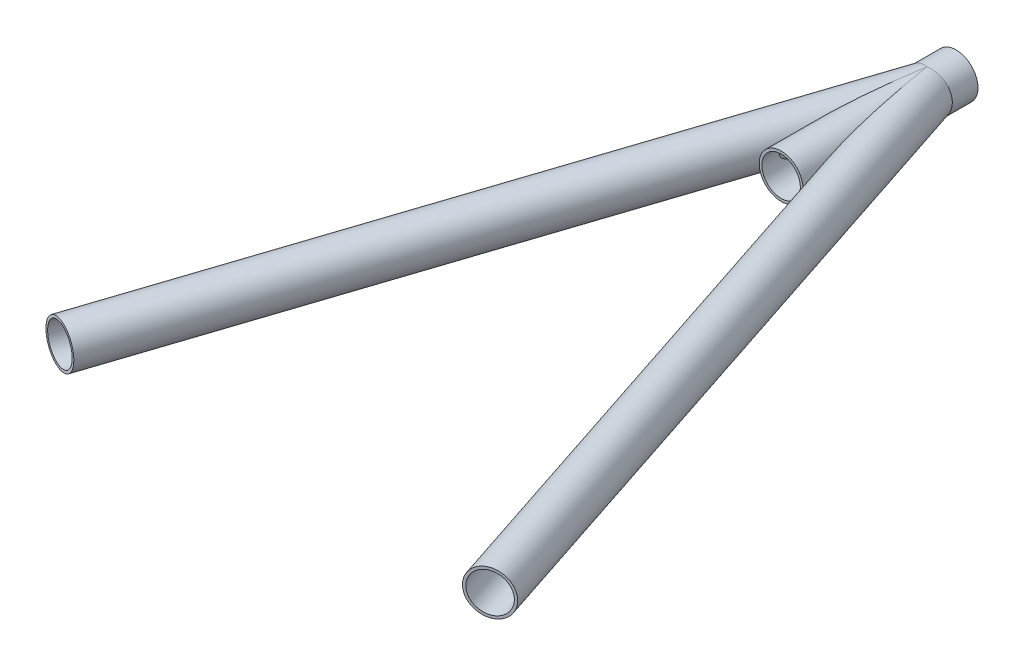
SolidWorks part; units mm, degrees
ref_plane "Front Plane" through (0, 0, 0) normal (0, 0, 1) x (1, 0, 0)
ref_plane "Top Plane" through (0, 0, 0) normal (0, 1, 0) x (1, 0, 0)
ref_plane "Right Plane" through (0, 0, 0) normal (1, 0, 0) x (0, 0, -1)
sketch "Sketch1" plane through (0, 0, 0) normal (0, 1, 0) x (1, 0, 0)
  line L0 (0, 0) -> (0, -25.4) construction
  line L1 (0, -25.4) -> (0, -38.1) construction
  line L2 (0, 0) -> (0, -346.075) construction
  line L3 (0, -38.1) -> (101.6, -346.075) construction
  line L4 (0, -38.1) -> (-101.6, -346.075) construction
  line L5 (101.6, -346.075) -> (0, -346.075) construction
  line L6 (0, -346.075) -> (-101.6, -346.075) construction
  line L7 (-101.6, -346.075) -> (-93.6425, -321.9537) construction
  line L8 (101.6, -346.075) -> (93.6425, -321.9537) construction
  line L9 (0, -38.1) -> (0, -101.6) construction
  circle A0 centre (0, 0) radius 15.003 construction
  circle A1 centre (101.6, -346.075) radius 15.003 construction
  circle A2 centre (-101.6, -346.075) radius 15.003 construction
  dimension "D1" = 25.4
  dimension "D2" = 101.6
  dimension "D3" = 346.075
  dimension "D4" = 25.4
  dimension "D5" = 25.4
  dimension "D6" = 12.7
  dimension "D7" = 63.5
ref_plane "Plane1" through (0, 0, 25.4) normal (0, 0, 1) x (1, 0, 0)
sketch "Sketch2" plane through (0, 0, 25.4) normal (0, 0, 1) x (1, 0, 0)
  circle A0 centre (0, 0) radius 9.525
  circle A1 centre (0, 0) radius 8.382
  dimension "D1" = 19.05
  dimension "D2" = 1.143
extrude "Boss-Extrude1" add sketch "Sketch2" along normal blind 76.2
sketch "Sketch3" plane through (0, 0, 0) normal (0, 1, 0) x (1, 0, 0)
  line L0 (0, -38.1) -> (93.6425, -321.9537)
sketch "Sketch46" plane through (0, 0, 0) normal (0, 1, 0) x (1, 0, 0)
  line L0 (0, -38.1) -> (-93.6425, -321.9537)
sweep "Sweep-Thin5" add path "Sketch46" circular profile diameter 19.05 parameters "D1"=1.143, "D3"=19.05
sweep "Sweep-Thin6" add path "Sketch3" circular profile diameter 19.05 parameters "D1"=1.143, "D3"=19.05
